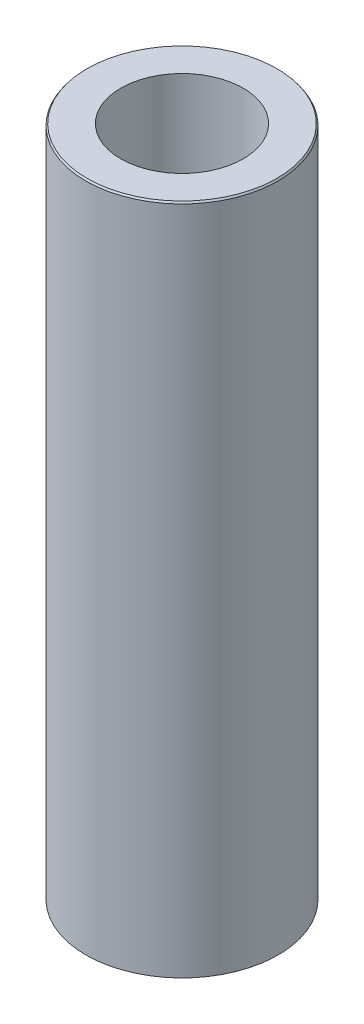
SolidWorks part; units mm, degrees
ref_plane "Front Plane" through (0, 0, 0) normal (0, 0, 1) x (1, 0, 0)
ref_plane "Top Plane" through (0, 0, 0) normal (0, 1, 0) x (1, 0, 0)
ref_plane "Right Plane" through (0, 0, 0) normal (1, 0, 0) x (0, 0, -1)
sketch "Sketch1" plane through (0, 0, 0) normal (0, 1, 0) x (1, 0, 0)
  circle A0 centre (0, 0) radius 50
  dimension "SHAFT_OD" = 100
extrude "Boss-Extrude1" add sketch "Sketch1" along normal blind 349.9031
sketch "Sketch2" plane through (0, 0, 0) normal (0, 1, 0) x (1, 0, 0)
  circle A0 centre (0, 0) radius 31.8438
  dimension "BORE_D" = 63.6877
extrude "Cut-Extrude1" cut sketch "Sketch2" along normal through all
chamfer "Chamfer1" distance 0.8777 angle 35.414 2 edges at (0, 349.9031, 50) (0, 0, 50) first distance on face at (0, 349.9031, 50) first distance on face at (0, 0, 31.8438)
